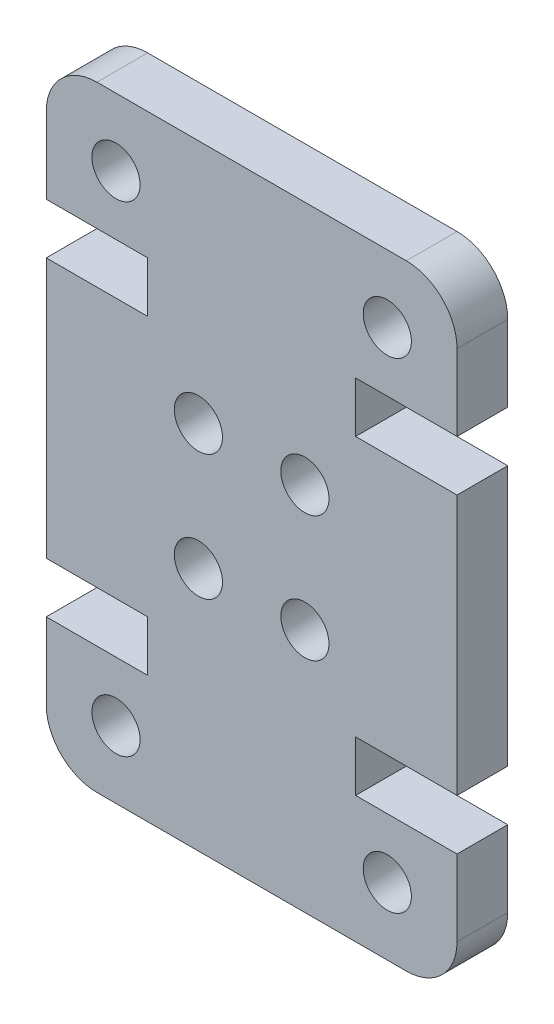
SolidWorks part; units mm, degrees
ref_plane "Front Plane" through (0, 0, 0) normal (0, 0, 1) x (1, 0, 0)
ref_plane "Top Plane" through (0, 0, 0) normal (0, 1, 0) x (1, 0, 0)
ref_plane "Right Plane" through (0, 0, 0) normal (1, 0, 0) x (0, 0, -1)
sketch "Sketch1" plane through (0, 0, 0) normal (0, 0, 1) x (1, 0, 0)
  line L0 (8.1, 24.26) -> (8.1, 0) construction
  line L1 (0, 12.13) -> (16.2, 12.13) construction
  line L2 (16.2, 17.26) -> (16.2, 7)
  line L3 (16.2, 2) -> (16.2, 5)
  line L4 (12.2, 5) -> (16.2, 5)
  line L5 (16.2, 7) -> (12.2, 7)
  line L6 (12.2, 7) -> (12.2, 5)
  line L7 (0, 22.26) -> (0, 19.26)
  line L8 (4, 19.26) -> (0, 19.26)
  line L9 (0, 17.26) -> (4, 17.26)
  line L10 (4, 17.26) -> (4, 19.26)
  line L11 (2, 24.26) -> (14.2, 24.26)
  line L12 (12.2, 17.26) -> (12.2, 19.26)
  line L13 (16.2, 17.26) -> (12.2, 17.26)
  line L14 (12.2, 19.26) -> (16.2, 19.26)
  line L15 (16.2, 22.26) -> (16.2, 19.26)
  line L21 (2, 0) -> (14.2, 0)
  line L25 (4, 7) -> (4, 5)
  line L28 (0, 7) -> (4, 7)
  line L30 (4, 5) -> (0, 5)
  line L34 (0, 2) -> (0, 5)
  line L38 (0, 17.26) -> (0, 7)
  circle A0 centre (13.45, 2.6536) radius 0.95
  circle A1 centre (10.2, 9.6536) radius 0.95
  arc A2 (16.2, 2) -> (14.2, 0) centre (14.2, 2) cw
  circle A3 centre (2.75, 21.6064) radius 0.95
  circle A4 centre (6, 14.6064) radius 0.95
  arc A5 (0, 22.26) -> (2, 24.26) centre (2, 22.26) cw
  arc A6 (16.2, 22.26) -> (14.2, 24.26) centre (14.2, 22.26) ccw
  circle A7 centre (10.2, 14.6064) radius 0.95
  circle A8 centre (13.45, 21.6064) radius 0.95
  arc A17 (0, 2) -> (2, 0) centre (2, 2) ccw
  circle A19 centre (6, 9.6536) radius 0.95
  circle A21 centre (2.75, 2.6536) radius 0.95
  point P16 (8.1, 12.13)
  dimension "D1" = 1.9
  dimension "D2" = 2
  dimension "D3" = 2.75
  dimension "D4" = 6
  dimension "D5" = 8.1
  dimension "D6" = 2.6536
  dimension "D9" = 9.6536
  dimension "D10" = 12.13
  dimension "D7" = 5
extrude "Boss-Extrude1" add sketch "Sketch1" along normal blind 2
equation "\"D5@Sketch1\"= \"fingerWidth@parametersSketch@prostheticParameters.SLDPRT\" / 2'PIP width"
equation "\"D10@Sketch1\"= ( \"HL@parametersSketch@prostheticParameters.SLDPRT\" * 0.196 - 4 - 8 ) / 2 'PIP length - Sil. Sht DIP - Sil. Sht PIP"
equation "\"D1@Sketch1\"= 1.5 + \"tol1@parametersSketch@prostheticParameters.SLDPRT\""
